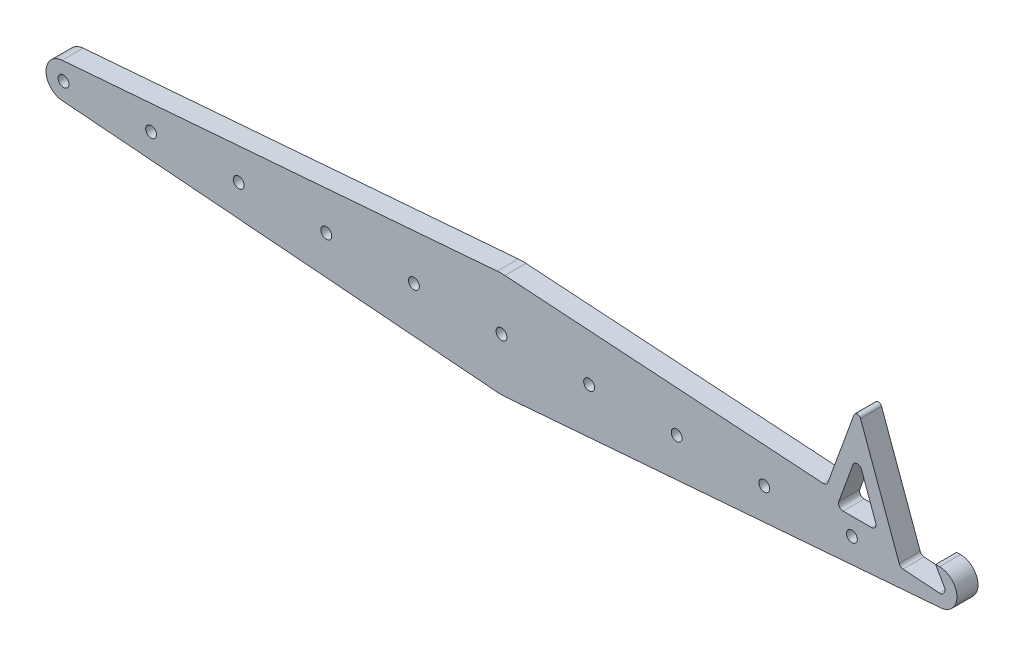
SolidWorks part; units mm, degrees
material "Pine"
ref_plane "Front Plane" through (0, 0, 0) normal (0, 0, 1) x (1, 0, 0)
ref_plane "Top Plane" through (0, 0, 0) normal (0, 1, 0) x (1, 0, 0)
ref_plane "Right Plane" through (0, 0, 0) normal (1, 0, 0) x (0, 0, -1)
sketch "Sketch1" plane through (0, 0, 0) normal (0, 0, 1) x (1, 0, 0)
  line L0 (0, 5) -> (250, 5)
  line L1 (250, -5) -> (0, -5)
  circle A0 centre (0, 0) radius 5
  circle A1 centre (250, 0) radius 5
  dimension "D1" = 250
  dimension "D2" = 10
extrude "Boss-Extrude1" add sketch "Sketch1" along normal blind 6 contours A1 L0 A0 L1 | A1 | A0 region at (125, 0, 0) region at (0, 0, 0) region at (250, 0, 0)
ref_plane "Plane1" through (0, 0, 3) normal (0, 0, 1) x (1, 0, 0)
sketch "Sketch2" plane through (0, 0, 6) normal (0, 0, 1) x (1, 0, 0)
  circle A0 centre (0, 0) radius 1.55
  circle A1 centre (250, 0) radius 1.55
  dimension "D1" = 3.1
extrude "Cut-Extrude1" cut sketch "Sketch2" against normal through all
pattern_linear "LPattern1" count 10 spacing 25 along (1, 0, 0) of "Cut-Extrude1"
sketch "Sketch3" plane through (0, 0, 6) normal (0, 0, 1) x (1, 0, 0)
  line L0 (251.3423, 0.775) -> (248.903, 5)
  line L1 (0, 5) -> (250, 5) construction
  line L2 (250, 0) -> (225, 0) construction
  line L3 (248.903, 5) -> (236.7057, 5)
  line L4 (225.6026, 30.342) -> (216.3789, 5)
  line L5 (250, -1.55) -> (240, -1.55)
  line L6 (238.7784, -0.6946) -> (227.482, 30.342)
  line L7 (216.3789, 5) -> (236.7057, 5)
  circle A0 centre (250, 0) radius 1.55 construction
  circle A1 centre (250, 0) radius 1.55
  arc A2 (227.482, 30.342) -> (225.6026, 30.342) centre (226.5423, 30) ccw
  arc A4 (240, -1.55) -> (238.7784, -0.6946) centre (240, -0.25) cw
  circle M17 centre (250, 0) radius 1.55
  line M20 (250, 5) -> (0, 5)
  dimension "D3" = 1
  dimension "D6" = 1.3
  dimension "D1" = 300
  dimension "D2" = 70
  dimension "D4" = 25
  dimension "D5" = 70
  dimension "D7" = 10
extrude "Cut-Extrude3" cut sketch "Sketch3" against normal through all contours L2 A1 L0 L6 M20 | L2 L6 A4 L5 M17 | A1 M17 | L0 L3 L7 L4 A2 L6 A4 L5 region at (243.6105, 2.5815, 6) region at (251.4548, 0.3898, 6) region at (243.845, -0.7762, 6)
extrude "Boss-Extrude2" add sketch "Sketch3<4>" against normal through all contours L6 A2 L4 M20 region at (226.5423, 14.2147, 6)
sketch "Sketch3<4>" plane through (0, 0, 6) normal (0, 0, 1) x (1, 0, 0) same geometry as "Sketch3"
sketch "Sketch4" plane through (0, 0, 6) normal (0, 0, 1) x (1, 0, 0)
  line L0 (0, 5) -> (216.3789, 5) construction
  line L5 (229.3614, 28.9739) -> (220.1376, 3.6319)
  line L6 (225.3207, 17.8723) -> (221.2706, 6.7446)
  line L7 (222.4922, 5) -> (230.5924, 5)
  line L8 (235.0196, -2.0627) -> (223.7232, 28.9739)
  line L9 (231.814, 6.7446) -> (227.7639, 17.8723)
  arc A0 (230.5924, 5) -> (231.814, 6.7446) centre (230.5924, 6.3) ccw
  arc A1 (221.2706, 6.7446) -> (222.4922, 5) centre (222.4922, 6.3) ccw
  arc A2 (227.7639, 17.8723) -> (225.3207, 17.8723) centre (226.5423, 17.4276) ccw
  dimension "D3" = 1.3
  dimension "D1" = 4
  dimension "D2" = 4
extrude "Cut-Extrude4" cut sketch "Sketch4" against normal through all
sketch "Sketch5" plane through (0, 0, 6) normal (0, 0, 1) x (1, 0, 0)
  line L0 (123.8, 14.9519) -> (-0.4, 4.984)
  line L1 (123.8, -14.9519) -> (-0.4, -4.984)
  line L2 (250.4, -4.984) -> (126.2, -14.9519)
  line L3 (250, -1.55) -> (239.6144, -0.7584)
  line L4 (125.9831, 14.9677) -> (216.8382, 9)
  line L5 (225.6026, 30.342) -> (216.3789, 5) construction
  line L7 (250, -1.55) -> (240, -1.55) construction
  line L8 (250, -1.55) -> (240, -1.55)
  line L9 (238.7784, -0.6946) -> (227.482, 30.342) construction
  line L10 (238.4916, 0.0933) -> (227.482, 30.342)
  line L11 (225.6026, 30.342) -> (218.1451, 9.8526)
  line L12 (0, 5) -> (216.3789, 5) construction
  line L13 (0, 5) -> (216.3789, 5)
  line L14 (250, -5) -> (0, -5) construction
  line L15 (250, -5) -> (0, -5)
  circle A0 centre (125, 0) radius 15
  arc A1 (0, 5) -> (0, -5) centre (0, 0) ccw construction
  arc A2 (250, -5) -> (250, 5) centre (250, 0) ccw construction
  arc A3 (238.7784, -0.6946) -> (240, -1.55) centre (240, -0.25) ccw construction
  arc A4 (238.7784, -0.6946) -> (240, -1.55) centre (240, -0.25) ccw
  arc A6 (238.4916, 0.0933) -> (239.6144, -0.7584) centre (239.7132, 0.5379) ccw
  arc A7 (218.1451, 9.8526) -> (216.8382, 9) centre (216.9235, 10.2972) cw
  arc A8 (0, 5) -> (0, -5) centre (0, 0) ccw
  arc A9 (250, -5) -> (250, 5) centre (250, 0) ccw
  line M20 (250, -1.55) -> (240, -1.55)
  arc M21 (240, -1.55) -> (238.7784, -0.6946) centre (240, -0.25) cw
  line M22 (238.7784, -0.6946) -> (227.482, 30.342)
  line M24 (225.6026, 30.342) -> (216.3789, 5)
  line M25 (216.3789, 5) -> (0, 5)
  arc M26 (0, 5) -> (0, -5) centre (0, 0) ccw
  line M27 (0, -5) -> (250, -5)
  arc M28 (250, -5) -> (250, 5) centre (250, 0) ccw
  dimension "D1" = 30
  dimension "D3" = 1.3
  dimension "D2" = 1.3
  dimension "D4" = 4
extrude "Boss-Extrude3" add sketch "Sketch5" against normal through all contours A0 L0 M26 M25 | A0 L1 M27 M26 | L13 A0 | L15 A0 | A0 L2 M28 M27 | A7 L4 A0 M24 M25 | A6 L3 M22 M21 M20 region at (76.19, 8.1937, 6) region at (125, 9.1422, 6) region at (170.8631, 8.6449, 6) region at (76.19, -8.1937, 6) region at (125, -9.1422, 6) region at (173.81, -8.1937, 6) region at (242.6356, -1.2425, 6)
